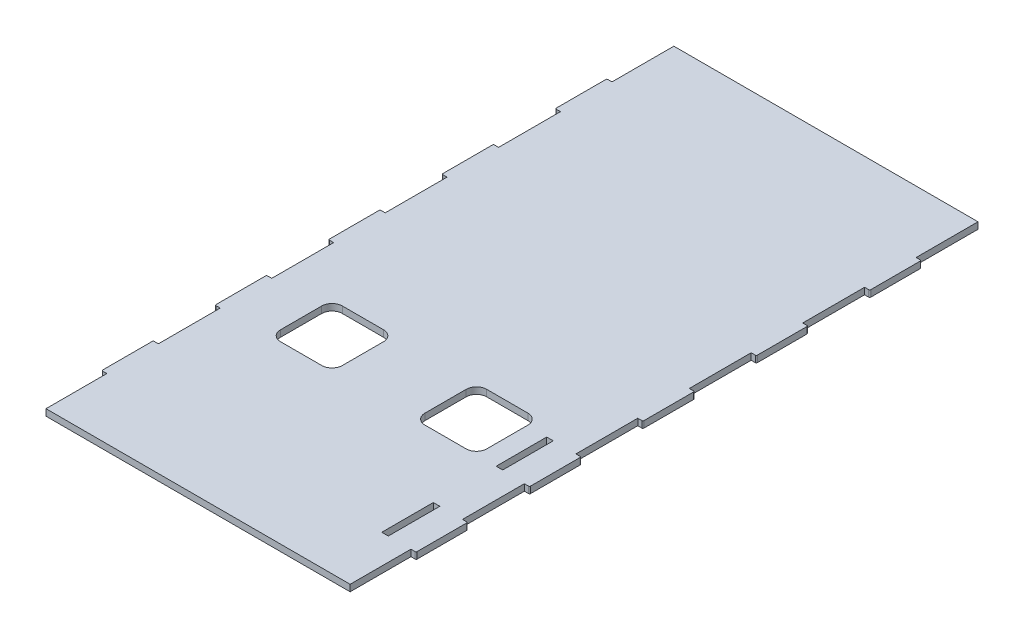
SolidWorks part; units mm, degrees
material "Oak"
ref_plane "Front Plane" through (0, 0, 0) normal (0, 0, 1) x (1, 0, 0)
ref_plane "Top Plane" through (0, 0, 0) normal (0, 1, 0) x (1, 0, 0)
ref_plane "Right Plane" through (0, 0, 0) normal (1, 0, 0) x (0, 0, -1)
sketch "Sketch1" plane through (0, 0, 0) normal (0, 1, 0) x (1, 0, 0)
  line L0 (157.0736, 348.6213) -> (157.0736, 288.6213)
  line L1 (-137.9264, 348.6213) -> (157.0736, 348.6213)
  line L3 (-137.9141, -260.3787) -> (157.0859, -260.3787)
  line L9 (157.0736, 288.6213) -> (162.0736, 288.6213)
  line L10 (162.0736, 288.6213) -> (162.0859, 238.6213)
  line L11 (162.0859, 238.6213) -> (157.0859, 238.6213)
  line L12 (157.0859, 238.6213) -> (157.0859, 178.6213)
  line L13 (157.0859, 178.6213) -> (162.0859, 178.6213)
  line L14 (162.0859, 178.6213) -> (162.0859, 128.6213)
  line L15 (162.0859, 128.6213) -> (157.0859, 128.6213)
  line L16 (157.0859, 128.6213) -> (157.0859, 68.6213)
  line L17 (157.0859, 68.6213) -> (162.0859, 68.6213)
  line L18 (162.0859, 68.6213) -> (162.0859, 18.6213)
  line L19 (162.0859, 18.6213) -> (157.0859, 18.6213)
  line L20 (157.0859, 18.6213) -> (157.0859, -41.3787)
  line L21 (157.0859, -41.3787) -> (162.0859, -41.3787)
  line L22 (162.0859, -41.3787) -> (162.0859, -91.3787)
  line L23 (162.0859, -91.3787) -> (157.0859, -91.3787)
  line L24 (157.0859, -91.3787) -> (157.0859, -151.3787)
  line L25 (157.0859, -151.3787) -> (162.0859, -151.3787)
  line L26 (162.0859, -151.3787) -> (162.0859, -201.3787)
  line L27 (162.0859, -201.3787) -> (157.0859, -201.3787)
  line L28 (157.0859, -201.3787) -> (157.0859, -260.3787)
  line L29 (-137.9264, 348.6213) -> (-137.9264, 288.6213)
  line L30 (-137.9264, 288.6213) -> (-142.9387, 288.6213)
  line L31 (-142.9387, 288.6213) -> (-142.9387, 238.6213)
  line L32 (-142.9387, 238.6213) -> (-137.9264, 238.6213)
  line L33 (-137.9264, 238.6213) -> (-137.9264, 178.6213)
  line L34 (-137.9264, 178.6213) -> (-142.9387, 178.6213)
  line L35 (-142.9387, 178.6213) -> (-142.9387, 128.6213)
  line L36 (-142.9387, 128.6213) -> (-137.9264, 128.6213)
  line L37 (-137.9264, 128.6213) -> (-137.9264, 68.6213)
  line L38 (-137.9264, 68.6213) -> (-142.9387, 68.6213)
  line L39 (-142.9387, 68.6213) -> (-142.9387, 18.6213)
  line L40 (-142.9387, 18.6213) -> (-137.9264, 18.6213)
  line L41 (-137.9264, 18.6213) -> (-137.9264, -41.3787)
  line L42 (-137.9264, -41.3787) -> (-142.9264, -41.3787)
  line L43 (-142.9264, -41.3787) -> (-142.9264, -91.3787)
  line L44 (-142.9264, -91.3787) -> (-137.9141, -91.3787)
  line L45 (-137.9141, -91.3787) -> (-137.9141, -151.3787)
  line L46 (-137.9141, -151.3787) -> (-142.9264, -151.3787)
  line L47 (-142.9264, -151.3787) -> (-142.9264, -201.3787)
  line L48 (-142.9264, -201.3787) -> (-137.9141, -201.3787)
  line L49 (-137.9141, -201.3787) -> (-137.9141, -260.3787)
  line L50 (128.7359, -259.5286) -> (128.7359, -159.5286) construction
  line L51 (128.7359, -159.5286) -> (-137.9141, -110.3787) construction
  line L52 (-137.9141, -110.3787) -> (-137.9141, -60.3787) construction
  line L53 (-137.9141, -60.3787) -> (162.0859, -60.3787) construction
  line L55 (-80.4688, -30.3787) -> (-40.4688, -30.3787)
  line L56 (-90.4688, -40.3787) -> (-90.4688, -80.3787)
  line L57 (-80.4688, -90.3787) -> (-40.4688, -90.3787)
  line L58 (-30.4688, -40.3787) -> (-30.4688, -80.3787)
  line L59 (-90.4688, -30.3787) -> (-30.4688, -90.3787) construction
  line L60 (-90.4688, -90.3787) -> (-30.4688, -30.3787) construction
  line L61 (59.5859, -30.3787) -> (99.5859, -30.3787)
  line L62 (49.5859, -40.3787) -> (49.5859, -80.3787)
  line L63 (59.5859, -90.3787) -> (99.5859, -90.3787)
  line L64 (109.5859, -40.3787) -> (109.5859, -80.3787)
  line L65 (49.5859, -30.3787) -> (109.5859, -90.3787) construction
  line L66 (49.5859, -90.3787) -> (109.5859, -30.3787) construction
  line L67 (128.7359, -201.3787) -> (135.0859, -201.3787)
  line L68 (128.7359, -201.3787) -> (128.7359, -151.3787)
  line L69 (128.7359, -151.3787) -> (135.0859, -151.3787)
  line L70 (135.0859, -201.3787) -> (135.0859, -151.3787)
  line L71 (128.7359, -90.3787) -> (135.0859, -90.3787)
  line L72 (128.7359, -90.3787) -> (128.7359, -41.3787)
  line L73 (128.7359, -41.3787) -> (135.0859, -41.3787)
  line L74 (135.0859, -90.3787) -> (135.0859, -41.3787)
  arc A0 (99.5859, -30.3787) -> (109.5859, -40.3787) centre (99.5859, -40.3787) cw
  arc A1 (109.5859, -80.3787) -> (99.5859, -90.3787) centre (99.5859, -80.3787) cw
  arc A2 (59.5859, -90.3787) -> (49.5859, -80.3787) centre (59.5859, -80.3787) cw
  arc A3 (49.5859, -40.3787) -> (59.5859, -30.3787) centre (59.5859, -40.3787) cw
  arc A4 (-90.4688, -80.3787) -> (-80.4688, -90.3787) centre (-80.4688, -80.3787) ccw
  arc A5 (-40.4688, -90.3787) -> (-30.4688, -80.3787) centre (-40.4688, -80.3787) ccw
  arc A6 (-40.4688, -30.3787) -> (-30.4688, -40.3787) centre (-40.4688, -40.3787) cw
  arc A7 (-80.4688, -30.3787) -> (-90.4688, -40.3787) centre (-80.4688, -40.3787) ccw
  point P46 (-90.4141, -60.3787)
  point P54 (61.387, -60.3787)
  dimension "D29" = 10
  dimension "D1" = 295
  dimension "D2" = 609
  dimension "D3" = 60
  dimension "D4" = 5
  dimension "D5" = 50
  dimension "D6" = 60
  dimension "D7" = 50
  dimension "D8" = 60
  dimension "D9" = 50
  dimension "D10" = 60
  dimension "D11" = 50
  dimension "D12" = 60
  dimension "D13" = 59
  dimension "D14" = 50
  dimension "D15" = 5
  dimension "D16" = 5
  dimension "D17" = 28.35
  dimension "D18" = 100
  dimension "D19" = 150
  dimension "D20" = 50
  dimension "D21" = 47.5
  dimension "D22" = 60
  dimension "D23" = 60
  dimension "D24" = 30
  dimension "D25" = 60
  dimension "D26" = 60
  dimension "D27" = 30
  dimension "D28" = 47.5
  dimension "D30" = 6.35
  dimension "D31" = 6.35
extrude "Boss-Extrude1" add sketch "Sketch1" along normal blind 6.35
fillet "Fillet1" radius 1 20 edges at (-142.9387, 3.175, -288.6213) (-142.9387, 3.175, -238.6213) (-142.9387, 3.175, -178.6213) (-142.9387, 3.175, -128.6213) (-142.9387, 3.175, -68.6213) (-142.9387, 3.175, -18.6213) (-142.9264, 3.175, 41.3787) (-142.9264, 3.175, 91.3787) (-140.4202, 0, 151.3787) (-142.9264, 3.175, 201.3787) (162.0736, 3.175, -288.6213) (162.0859, 3.175, -238.6213) (162.0859, 3.175, -178.6213) (162.0859, 3.175, -128.6213) (162.0859, 3.175, -68.6213) (162.0859, 3.175, -18.6213) (162.0859, 3.175, 41.3787) (162.0859, 3.175, 91.3787) (162.0859, 3.175, 151.3787) (162.0859, 3.175, 201.3787)
sketch "Sketch3" plane through (0, 6.35, 0) normal (0, 1, 0) x (1, 0, 0)
  line L0 (-137.9141, -260.3787) -> (157.0859, -260.3787) construction
  line L1 (154.142, -120.3787) -> (54.142, -120.3787)
  line L2 (164.142, -110.3787) -> (164.142, -10.3787)
  line L3 (154.142, -0.3787) -> (54.142, -0.3787)
  line L4 (44.142, -110.3787) -> (44.142, -10.3787)
  line L5 (-129.858, -120.3787) -> (-29.858, -120.3787)
  line L6 (-139.858, -110.3787) -> (-139.858, -10.3787)
  line L7 (-129.858, -0.3787) -> (-29.858, -0.3787)
  line L8 (-19.858, -110.3787) -> (-19.858, -10.3787)
  arc A0 (44.142, -110.3787) -> (54.142, -120.3787) centre (54.142, -110.3787) ccw
  arc A1 (154.142, -120.3787) -> (164.142, -110.3787) centre (154.142, -110.3787) ccw
  arc A2 (164.142, -10.3787) -> (154.142, -0.3787) centre (154.142, -10.3787) ccw
  arc A3 (54.142, -0.3787) -> (44.142, -10.3787) centre (54.142, -10.3787) ccw
  arc A4 (-29.858, -0.3787) -> (-19.858, -10.3787) centre (-29.858, -10.3787) cw
  arc A5 (-19.858, -110.3787) -> (-29.858, -120.3787) centre (-29.858, -110.3787) cw
  arc A6 (-129.858, -120.3787) -> (-139.858, -110.3787) centre (-129.858, -110.3787) cw
  arc A7 (-139.858, -10.3787) -> (-129.858, -0.3787) centre (-129.858, -10.3787) cw
  point P12 (44.142, -120.3787)
  point P15 (164.142, -120.3787)
  point P18 (164.142, -0.3787)
  point P23 (-19.858, -0.3787)
  point P28 (-139.858, -120.3787)
  point P31 (-139.858, -0.3787)
  dimension "D7" = 10
  dimension "D1" = 120
  dimension "D2" = 120
  dimension "D3" = 140
  dimension "D4" = 140
  dimension "D5" = 120
  dimension "D6" = 120
sketch "Sketch4" plane through (0, 6.35, 0) normal (0, 1, 0) x (1, 0, 0)
  line L1 (20.9069, 141.6824) -> (76.9069, 141.6824)
  line L2 (13.9069, 134.6824) -> (13.9069, 78.6824)
  line L3 (20.9069, 71.6824) -> (76.9069, 71.6824)
  line L4 (83.9069, 134.6824) -> (83.9069, 78.6824)
  line L9 (-82.7769, 202.8094) -> (-26.7769, 202.8094)
  line L10 (-89.7769, 195.8094) -> (-89.7769, 139.8094)
  line L11 (-82.7769, 132.8094) -> (-26.7769, 132.8094)
  line L12 (-19.7769, 195.8094) -> (-19.7769, 139.8094)
  arc A0 (83.9069, 78.6824) -> (76.9069, 71.6824) centre (76.9069, 78.6824) cw
  arc A1 (20.9069, 71.6824) -> (13.9069, 78.6824) centre (20.9069, 78.6824) cw
  arc A2 (83.9069, 134.6824) -> (76.9069, 141.6824) centre (76.9069, 134.6824) ccw
  arc A3 (20.9069, 141.6824) -> (13.9069, 134.6824) centre (20.9069, 134.6824) ccw
  arc A4 (-26.7769, 202.8094) -> (-19.7769, 195.8094) centre (-26.7769, 195.8094) cw
  arc A5 (-26.7769, 132.8094) -> (-19.7769, 139.8094) centre (-26.7769, 139.8094) ccw
  arc A6 (-89.7769, 139.8094) -> (-82.7769, 132.8094) centre (-82.7769, 139.8094) ccw
  arc A7 (-89.7769, 195.8094) -> (-82.7769, 202.8094) centre (-82.7769, 195.8094) cw
  point P6 (83.9069, 71.6824)
  point P15 (83.9069, 141.6824)
  point P18 (13.9069, 141.6824)
  point P21 (-19.7769, 202.8094)
  point P26 (-89.7769, 132.8094)
  point P29 (-89.7769, 202.8094)
  dimension "D5" = 7
  dimension "D1" = 70
  dimension "D2" = 70
  dimension "D3" = 70
  dimension "D4" = 70
